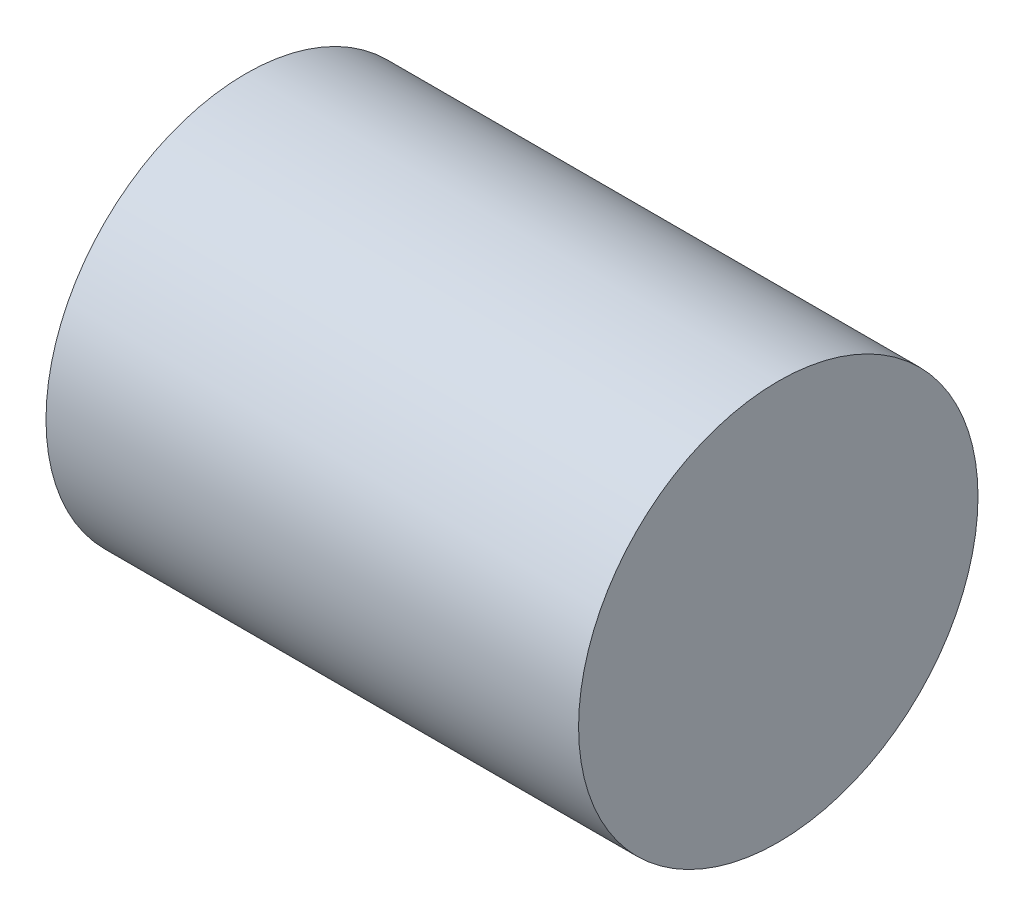
SolidWorks part; units mm, degrees
ref_plane "Front Plane" through (0, 0, 0) normal (0, 0, 1) x (1, 0, 0)
ref_plane "Top Plane" through (0, 0, 0) normal (0, 1, 0) x (1, 0, 0)
ref_plane "Right Plane" through (0, 0, 0) normal (1, 0, 0) x (0, 0, -1)
sketch "Sketch1" plane through (0, 0, 0) normal (1, 0, 0) x (0, 0, -1)
  circle A0 centre (0, 0) radius 75
extrude "Boss-Extrude1" add sketch "Sketch1" along normal blind 100 and the other way blind 100
